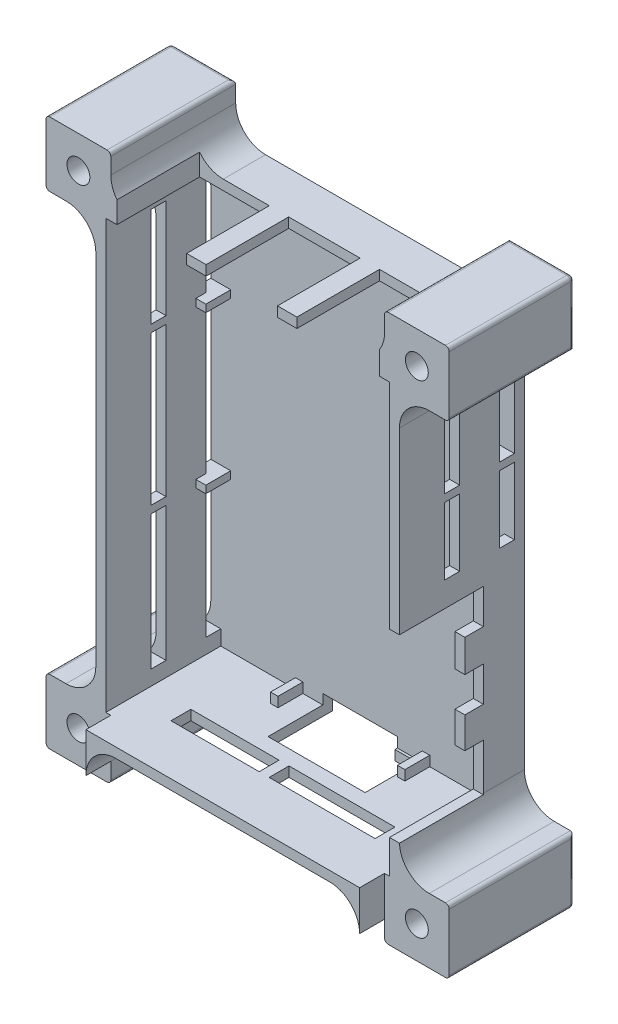
SolidWorks part; units mm, degrees
ref_plane "Front Plane" through (0, 0, 0) normal (0, 0, 1) x (1, 0, 0)
ref_plane "Top Plane" through (0, 0, 0) normal (0, 1, 0) x (1, 0, 0)
ref_plane "Right Plane" through (0, 0, 0) normal (1, 0, 0) x (0, 0, -1)
sketch "Sketch1" plane through (0, 0, 0) normal (0, 0, 1) x (1, 0, 0)
  line L1 (0, 0) -> (61, 0)
  line L2 (0, 0) -> (0, 90)
  line L3 (0, 90) -> (61, 90)
  line L4 (61, 0) -> (61, 90)
  dimension "D1" = 61
  dimension "D2" = 90
extrude "Boss-Extrude1" add sketch "Sketch1" along normal blind 2
sketch "Sketch2" plane through (0, 0, 2) normal (0, 0, 1) x (1, 0, 0)
  line L7 (0, -16.225) -> (0, 16.225) construction
  line L8 (0, 90) -> (0, 0)
  line L9 (2, 90) -> (2, 2)
  line L10 (2, 2) -> (59, 2)
  line L11 (59, 2) -> (59, 90)
  line L12 (2, 88) -> (2, 2)
  line L13 (2, 2) -> (59, 2)
  line L14 (59, 2) -> (59, 88)
  line L15 (0, 0) -> (61, 0)
  line L18 (61, 90) -> (61, 0)
  line L20 (2, 88) -> (59, 88)
  line L21 (0, 90) -> (61, 90)
  dimension "D1" = 2
extrude "Boss-Extrude2" add sketch "Sketch2" along normal blind 6.6
sketch "Sketch3" plane through (0, 0, 2) normal (0, 0, 1) x (1, 0, 0)
  line L0 (59, 2) -> (2, 2) construction
  line L1 (44, 2) -> (42.5, 2)
  line L2 (44, 2) -> (44, 4)
  line L3 (44, 4) -> (42.5, 4)
  line L4 (42.5, 2) -> (42.5, 4)
  line L5 (2, 2) -> (2, 88) construction
  line L6 (17, 2) -> (18.5, 2)
  line L7 (17, 2) -> (17, 4)
  line L8 (17, 4) -> (18.5, 4)
  line L9 (18.5, 2) -> (18.5, 4)
  line L10 (2, 32) -> (4, 32)
  line L11 (2, 32) -> (2, 33.5)
  line L12 (2, 33.5) -> (4, 33.5)
  line L13 (4, 32) -> (4, 33.5)
  line L14 (59, 88) -> (59, 2) construction
  line L15 (59, 32) -> (57, 32)
  line L16 (59, 32) -> (59, 33.5)
  line L17 (59, 33.5) -> (57, 33.5)
  line L18 (57, 32) -> (57, 33.5)
  line L19 (2, 2) -> (2, 88) construction
  line L20 (59, 63.5) -> (57, 63.5)
  line L21 (59, 63.5) -> (59, 65)
  line L22 (59, 65) -> (57, 65)
  line L23 (57, 63.5) -> (57, 65)
  line L24 (2, 63.5) -> (4, 63.5)
  line L25 (2, 63.5) -> (2, 65)
  line L26 (2, 65) -> (4, 65)
  line L27 (4, 63.5) -> (4, 65)
  line L28 (59, 2) -> (2, 2) construction
  dimension "D1" = 1.5
  dimension "D2" = 1.5
  dimension "D3" = 1.5
  dimension "D4" = 1.5
  dimension "D5" = 1.5
  dimension "D6" = 1.5
  dimension "D7" = 2
  dimension "D8" = 2
  dimension "D9" = 2
  dimension "D10" = 2
  dimension "D11" = 2
  dimension "D12" = 2
  dimension "D13" = 30
  dimension "D14" = 30
  dimension "D15" = 30
  dimension "D16" = 30
  dimension "D17" = 15
  dimension "D18" = 15
extrude "Boss-Extrude3" add sketch "Sketch3" along normal blind 5
sketch "Sketch4" plane through (0, 0, 8.6) normal (0, 0, 1) x (1, 0, 0)
  line L1 (61, 90) -> (0, 90)
  line L3 (59, 88) -> (2, 88)
  line L5 (61, 90) -> (61, 0)
  line L6 (0, 90) -> (0, 0)
  line L7 (0, 0) -> (61, 0)
  line L8 (2, 2) -> (59, 2)
  line L9 (2, 88) -> (2, 2)
  line L10 (59, 2) -> (59, 88)
  line L11 (59, 2) -> (59, 88) construction
extrude "Boss-Extrude4" add sketch "Sketch4" along normal blind 16.5
sketch "Sketch5" plane through (0, 90, 0) normal (0, 1, 0) x (1, 0, 0)
  line L1 (57, -8.5) -> (40.4, -8.5)
  line L3 (57, -22.25) -> (40.4, -22.25) construction
  line L4 (40.4, -8.5) -> (40.4, -22.25)
  line L5 (61, 0) -> (0, 0) construction
  line L6 (61, -25.1) -> (0, -25.1) construction
  line L7 (36.5, -25.1) -> (22.15, -25.1)
  line L8 (36.5, -25.1) -> (36.5, -8.5)
  line L9 (36.5, -8.5) -> (22.15, -8.5)
  line L10 (22.15, -25.1) -> (22.15, -8.5)
  line L11 (0, -25.1) -> (0, 0) construction
  line L12 (18.25, -25.1) -> (4.25, -25.1)
  line L13 (18.25, -25.1) -> (18.25, -8.5)
  line L14 (18.25, -8.5) -> (4.25, -8.5)
  line L15 (4.25, -25.1) -> (4.25, -8.5)
  line L17 (57, -25.1) -> (40.4, -25.1)
  line L19 (57, -22.25) -> (40.4, -22.25) construction
  line L20 (40.4, -25.1) -> (40.4, -22.25)
  line L21 (57, -8.5) -> (57, -25.1)
  line L22 (61, -25.1) -> (61, 0) construction
  point P21 (61, -12.55)
  dimension "D2" = 16.6
  dimension "D3" = 13.75
  dimension "D4" = 8.5
  dimension "D5" = 4.25
  dimension "D6" = 3.9
  dimension "D7" = 14
  dimension "D8" = 8.5
  dimension "D9" = 8.5
  dimension "D10" = 3.9
  dimension "D11" = 4
  dimension "D12" = 0
extrude "Cut-Extrude1" cut sketch "Sketch5" against normal blind 2
sketch "Sketch7" plane through (61, 0, 0) normal (1, 0, 0) x (0, 0, -1)
  line L0 (-11.95, 18.25) -> (-11.95, 24.5)
  line L8 (-11.95, 18.25) -> (-8.25, 18.25)
  line L9 (-8.25, 8.75) -> (-8.25, 18.25)
  line L10 (-11.95, 24.5) -> (-8.25, 24.5)
  line L12 (-11.95, 38) -> (-8.25, 38)
  line L14 (-11.95, 31.5) -> (-8.25, 31.5)
  line L18 (-25.1, 0) -> (-25.1, 90) construction
  line L19 (-25.1, 8.75) -> (-25.1, 45)
  line L21 (-11.95, 38) -> (-11.95, 31.5)
  line L22 (-8.25, 8.75) -> (-25.1, 8.75)
  line L23 (-25.1, 45) -> (-8.25, 45)
  line L24 (-25.1, 0) -> (0, 0) construction
  line L25 (-8.25, 24.5) -> (-8.25, 31.5)
  line L26 (-8.25, 38) -> (-8.25, 45)
  line L28 (0, 0) -> (0, 90) construction
  line L29 (0, 33.55) -> (0, -33.55) construction
  line L30 (-2, 85) -> (-5, 85)
  line L31 (-2, 85) -> (-2, 50)
  line L32 (-2, 50) -> (-5, 50)
  line L33 (-5, 85) -> (-5, 50)
  line L34 (-25.1, 90) -> (0, 90) construction
  line L35 (-16, 50) -> (-13, 50)
  line L36 (-16, 50) -> (-16, 63.5)
  line L37 (-16, 63.5) -> (-13, 63.5)
  line L38 (-13, 50) -> (-13, 63.5)
  line L39 (-16, 65) -> (-13, 65)
  line L40 (-16, 65) -> (-16, 85)
  line L41 (-16, 85) -> (-13, 85)
  line L42 (-13, 65) -> (-13, 85)
  point P0 (-8.25, 13.5)
  point P16 (-8.25, 41.5)
  point P18 (-10.1, 18.25)
  point P20 (-8.25, 28)
  dimension "D1" = 9.5
  dimension "D2" = 28
  dimension "D3" = 7
  dimension "D4" = 7
  dimension "D5" = 13.5
  dimension "D6" = 41.5
  dimension "D7" = 3.7
  dimension "D8" = 3.7
  dimension "D9" = 8.25
  dimension "D10" = 0
  dimension "D11" = 0
  dimension "D12" = 2
  dimension "D13" = 5
  dimension "D14" = 3
  dimension "D15" = 35
  dimension "D16" = 3
  dimension "D17" = 8
  dimension "D18" = 0
  dimension "D19" = 1.5
  dimension "D20" = 20
  dimension "D21" = 3
  dimension "D22" = 8
extrude "Cut-Extrude2" cut sketch "Sketch7" against normal blind 2
sketch "Sketch8" plane through (0, 0, 0) normal (0, -1, 0) x (-1, 0, 0)
  line L0 (0, -25.1) -> (0, 0) construction
  line L2 (-22.5, -13) -> (-22.5, -2.5)
  line L3 (-22.5, -2.5) -> (-42, -2.5)
  line L4 (-42, -13) -> (-42, -2.5)
  line L5 (0, 13.805) -> (0, -13.805) construction
  line L6 (-61, -25.1) -> (-61, 0) construction
  line L7 (-33.55, 0) -> (33.55, 0) construction
  line L8 (-22.5, -13) -> (-42, -13)
  line L9 (-10, -20) -> (-27.72, -20)
  line L10 (-10, -20) -> (-10, -16)
  line L11 (-10, -16) -> (-27.72, -16)
  line L12 (-51, -20) -> (-51, -16)
  line L13 (-27.72, -20) -> (-27.72, -16)
  line L14 (-29.72, -20) -> (-29.72, -16)
  line L15 (-29.72, -20) -> (-51, -20)
  line L16 (-29.72, -16) -> (-51, -16)
  dimension "D1" = 22.5
  dimension "D2" = 19
  dimension "D3" = 2.5
  dimension "D4" = 10.5
  dimension "D5" = 3
  dimension "D6" = 4
  dimension "D7" = 10
  dimension "D8" = 10
  dimension "D9" = 2
extrude "Cut-Extrude3" cut sketch "Sketch8" against normal blind 2
sketch "Sketch9" plane through (0, 0, 0) normal (-1, 0, 0) x (0, 0, 1)
  line L0 (0, -33.55) -> (0, 33.55) construction
  line L1 (5, 85) -> (2, 85)
  line L2 (5, 85) -> (5, 5)
  line L3 (5, 5) -> (2, 5)
  line L4 (2, 85) -> (2, 5)
  line L5 (25.1, 90) -> (0, 90) construction
  line L6 (13.805, 0) -> (-13.805, 0) construction
  line L8 (13, 85) -> (16, 85)
  line L9 (13, 85) -> (13, 65)
  line L10 (13, 65) -> (16, 65)
  line L11 (16, 85) -> (16, 65)
  line L12 (16, 63.5) -> (13, 63.5)
  line L13 (16, 63.5) -> (16, 33.5)
  line L14 (16, 33.5) -> (13, 33.5)
  line L15 (13, 63.5) -> (13, 33.5)
  line L16 (13, 32) -> (16, 32)
  line L17 (13, 32) -> (13, 5)
  line L18 (13, 5) -> (16, 5)
  line L19 (16, 32) -> (16, 5)
  dimension "D1" = 2
  dimension "D2" = 3
  dimension "D3" = 5
  dimension "D4" = 5
  dimension "D5" = 1.5
  dimension "D6" = 1.5
  dimension "D7" = 0
  dimension "D8" = 0
  dimension "D9" = 8
  dimension "D10" = 3
  dimension "D11" = 8
  dimension "D12" = 8
  dimension "D13" = 3
  dimension "D14" = 3
  dimension "D15" = 20
  dimension "D16" = 30
extrude "Cut-Extrude4" cut sketch "Sketch9" against normal blind 2
sketch "Sketch10" plane through (0, 0, 25.1) normal (0, 0, 1) x (1, 0, 0)
  line L0 (61, 0) -> (61, 8.75) construction
  line L1 (0, 0) -> (61, 0)
  line L2 (0, 0) -> (0, 2)
  line L3 (0, 2) -> (61, 2)
  line L4 (61, 0) -> (61, 2)
  dimension "D1" = 2
extrude "Boss-Extrude5" add sketch "Sketch10" along normal blind 5
sketch "Sketch12" plane through (2, 0, 0) normal (-1, 0, 0) x (0, 0, 1)
  line L0 (5, 63.5) -> (2, 63.5) construction
  line L1 (2, 65) -> (5, 65)
  line L2 (2, 65) -> (2, 63.5)
  line L3 (2, 63.5) -> (5, 63.5)
  line L4 (5, 65) -> (5, 63.5)
  line L5 (5, 32) -> (2, 32) construction
  line L6 (2, 33.5) -> (5, 33.5)
  line L7 (2, 33.5) -> (2, 32)
  line L8 (2, 32) -> (5, 32)
  line L9 (5, 33.5) -> (5, 32)
extrude "Boss-Extrude6" add sketch "Sketch12" along normal blind 2
sketch "Sketch13" plane through (59, 0, 0) normal (1, 0, 0) x (0, 0, -1)
  line L1 (-2, 63.5) -> (-5, 63.5)
  line L2 (-2, 63.5) -> (-2, 65)
  line L3 (-2, 65) -> (-5, 65)
  line L4 (-5, 63.5) -> (-5, 65)
extrude "Boss-Extrude7" add sketch "Sketch13" along normal blind 2
sketch "Sketch20" plane through (0, 0, 0) normal (0, 0, -1) x (-1, 0, 0)
  line L0 (-61, 90) -> (0, 90) construction
  line L1 (-3, 3) -> (10, 3)
  line L2 (-3, 3) -> (-3, -10)
  line L3 (-3, -10) -> (10, -10)
  line L4 (10, 3) -> (10, -10)
  line L5 (-3, 3) -> (10, -10) construction
  line L6 (-3, -10) -> (10, 3) construction
  line L7 (-58, 87) -> (-71, 87)
  line L8 (-58, 87) -> (-58, 100)
  line L9 (-58, 100) -> (-71, 100)
  line L10 (-71, 87) -> (-71, 100)
  line L11 (-58, 87) -> (-71, 100) construction
  line L12 (-58, 100) -> (-71, 87) construction
  line L13 (-61, 0) -> (-61, 90) construction
  line L14 (0, 0) -> (-61, 0) construction
  line L15 (0, 90) -> (0, 0) construction
  point P4 (3.5, -3.5)
  point P9 (-64.5, 93.5)
  dimension "D1" = 3
  dimension "D2" = 3
  dimension "D3" = 13
  dimension "D4" = 13
  dimension "D5" = 3
  dimension "D6" = 13
  dimension "D7" = 3
  dimension "D8" = 13
extrude "Boss-Extrude8" add sketch "Sketch20" against normal up to surface (25.1 mm away) up to face at (2.0833, 60, 25.1)
sketch "Sketch25" plane through (0, 0, 25.1) normal (0, 0, 1) x (1, 0, 0)
  line L1 (3, 3) -> (-10, 3)
  line L2 (3, 3) -> (3, -10)
  line L3 (3, -10) -> (-10, -10)
  line L4 (-10, 3) -> (-10, -10)
  line L5 (3, 3) -> (-10, -10) construction
  line L6 (3, -10) -> (-10, 3) construction
  line L7 (3, -10) -> (3.25, -10)
  line L8 (3, -10) -> (3, 3)
  line L9 (3, 3) -> (3.25, 3)
  line L10 (3.25, -10) -> (3.25, 3)
  line L11 (3, -10) -> (3.25, 3) construction
  line L12 (3, 3) -> (3.25, -10) construction
  point P4 (-3.5, -3.5)
  point P10 (3.125, -3.5)
  dimension "D1" = 0.25
extrude "Cut-Extrude11" cut sketch "Sketch25" along normal through all contours L2 L1 L4 L3 | L8 L7 L10 L9
sketch "Sketch26" plane through (0, 0, 25.1) normal (0, 0, 1) x (1, 0, 0)
  line L1 (3, 3) -> (2, 3)
  line L2 (3, 3) -> (3, 2)
  line L3 (3, 2) -> (2, 2)
  line L4 (2, 3) -> (2, 2)
  line L5 (3, 3) -> (2, 2) construction
  line L6 (3, 2) -> (2, 3) construction
  line L7 (58, 87) -> (59, 87)
  line L8 (58, 87) -> (58, 88)
  line L9 (58, 88) -> (59, 88)
  line L10 (59, 87) -> (59, 88)
  line L11 (58, 87) -> (59, 88) construction
  line L12 (58, 88) -> (59, 87) construction
  point P4 (2.5, 2.5)
  point P10 (58.5, 87.5)
  dimension "D1" = 1
  dimension "D2" = 1
  dimension "D3" = 1
  dimension "D4" = 1
extrude "Cut-Extrude12" cut sketch "Sketch26" against normal up to surface (23.1 mm away) up to face at (30.4, 40.25, 2)
sketch "Sketch27" plane through (0, 0, 25.1) normal (0, 0, 1) x (1, 0, 0)
  line L0 (64.5, 100) -> (64.5, 87) construction
  line L1 (58, 100) -> (71, 100) construction
  line L2 (71, 87) -> (61, 87) construction
  line L3 (71, 93.5) -> (58, 93.5) construction
  line L4 (71, 100) -> (71, 87) construction
  line L5 (58, 90) -> (58, 100) construction
  line L6 (-3.5, -10) -> (-3.5, 3) construction
  line L7 (3, -10) -> (-10, -10) construction
  line L8 (-10, 3) -> (0, 3) construction
  line L9 (-10, -3.5) -> (3, -3.5) construction
  line L10 (-10, -10) -> (-10, 3) construction
  line L11 (3, 0) -> (3, -10) construction
  circle A0 centre (-3.5, -3.5) radius 2.3
  circle A1 centre (64.5, 93.5) radius 2.3
  dimension "D1" = 4.6
  dimension "D2" = 4.6
extrude "Cut-Extrude13" cut sketch "Sketch27" against normal through all
sketch "Sketch31" plane through (0, 0, 0) normal (0, 0, -1) x (-1, 0, 0)
  line L0 (-71, 100) -> (-71, 87) construction
  line L1 (-61.8731, 88.95) -> (-59.2461, 93.5)
  line L2 (-59.2461, 93.5) -> (-61.8731, 98.05)
  line L3 (-61.8731, 98.05) -> (-67.1269, 98.05)
  line L4 (-67.1269, 98.05) -> (-69.7539, 93.5)
  line L5 (-69.7539, 93.5) -> (-67.1269, 88.95)
  line L6 (-67.1269, 88.95) -> (-61.8731, 88.95)
  line L7 (6.1269, -8.05) -> (8.7539, -3.5)
  line L8 (8.7539, -3.5) -> (6.1269, 1.05)
  line L9 (6.1269, 1.05) -> (0.8731, 1.05)
  line L10 (0.8731, 1.05) -> (-1.7539, -3.5)
  line L11 (-1.7539, -3.5) -> (0.8731, -8.05)
  line L12 (0.8731, -8.05) -> (6.1269, -8.05)
  line L13 (10, -10) -> (10, 3) construction
  circle A0 centre (-64.5, 93.5) radius 4.55 construction
  circle A1 centre (3.5, -3.5) radius 4.55 construction
  dimension "D1" = 9.1
  dimension "D2" = 9.1
  dimension "D3" = 30
  dimension "D4" = 30
extrude "Cut-Extrude17" cut sketch "Sketch31" against normal blind 6
fillet "Fillet3" radius 6 1 edges at (58, 90, 12.55) type face fillet first side face at (29.5687, 90, 15.7375) second side face at (58, 95, 12.55)
fillet "Fillet4" radius 6 1 edges at (61, 87, 12.55) type face fillet first side face at (61, 75, 3.5) second side face at (66, 87, 12.55)
sketch "Sketch33" plane through (0, 0, 25.1) normal (0, 0, 1) x (1, 0, 0)
  line L0 (2, 2) -> (3.25, 2) construction
  line L1 (3.25, 0) -> (3, 0)
  line L2 (3.25, 0) -> (3.25, 2)
  line L3 (3.25, 2) -> (3, 2)
  line L4 (3, 0) -> (3, 2)
  line L5 (3.25, 0) -> (3, 2) construction
  line L6 (3.25, 2) -> (3, 0) construction
  point P4 (3.125, 1)
  dimension "D1" = 0.25
extrude "Boss-Extrude10" add sketch "Sketch33" along normal up to surface (5 mm away) up to face at (32.125, 1, 30.1)
fillet "Fillet7" radius 6 1 edges at (3, 0, 12.55) type face fillet first side face at (3, -5, 12.55) second side face at (18.86, 0, 18)
fillet "Fillet8" radius 6 1 edges at (0, 3, 12.55) type face fillet first side face at (-5, 3, 12.55) second side face at (0, 48.5, 3.5)
sketch "Sketch34" plane through (0, 0, 25.1) normal (0, 0, 1) x (1, 0, 0)
  line L0 (18.25, 90) -> (4.25, 90) construction
  line L1 (59, 3) -> (71, 3)
  line L2 (58, 2) -> (58, -10)
  line L3 (58, -10) -> (71, -10)
  line L4 (71, 3) -> (71, -10)
  line L5 (59, 2) -> (71, -10) construction
  line L6 (58, -10) -> (71, 3) construction
  line L7 (2, 87) -> (-10, 87)
  line L8 (3, 88) -> (3, 100)
  line L9 (3, 100) -> (-10, 100)
  line L10 (-10, 87) -> (-10, 100)
  line L11 (2, 88) -> (-10, 100) construction
  line L12 (3, 100) -> (-10, 87) construction
  line L13 (0, 90) -> (0, 9) construction
  line L14 (61, 0) -> (61, 2) construction
  line L15 (9, 0) -> (61, 0) construction
  line L16 (59, 88) -> (2, 88) construction
  line L17 (2, 88) -> (2, 2) construction
  line L18 (3, 88) -> (2, 88)
  line L19 (2, 88) -> (2, 87)
  line L20 (59, 2) -> (59, 8.75) construction
  line L21 (44, 2) -> (59, 2) construction
  line L22 (59, 2) -> (59, 3)
  line L23 (58, 2) -> (59, 2)
  point P4 (64.5, -3.5)
  point P9 (-3.5, 93.5)
  dimension "D1" = 3
  dimension "D2" = 3
  dimension "D3" = 3
  dimension "D4" = 3
  dimension "D5" = 13
  dimension "D6" = 13
  dimension "D7" = 13
  dimension "D8" = 13
extrude "Boss-Extrude11" add sketch "Sketch34" against normal up to surface (25.1 mm away) up to face at (30.5, 45, 0)
sketch "Sketch35" plane through (0, 0, 25.1) normal (0, 0, 1) x (1, 0, 0)
  line L0 (-3.5, 100) -> (-3.5, 87) construction
  line L1 (3, 100) -> (-10, 100) construction
  line L2 (-10, 87) -> (0, 87) construction
  line L3 (-10, 93.5) -> (3, 93.5) construction
  line L4 (-10, 100) -> (-10, 87) construction
  line L5 (3, 90) -> (3, 100) construction
  line L6 (64.5, -10) -> (64.5, 3) construction
  line L7 (58, -10) -> (71, -10) construction
  line L8 (71, 3) -> (61, 3) construction
  line L9 (71, -3.5) -> (58, -3.5) construction
  line L10 (71, -10) -> (71, 3) construction
  line L11 (58, 0) -> (58, -10) construction
  circle A0 centre (-3.5, 93.5) radius 2.3
  circle A1 centre (64.5, -3.5) radius 2.3
  dimension "D1" = 4.6
  dimension "D2" = 4.6
extrude "Cut-Extrude18" cut sketch "Sketch35" against normal through all
fillet "Fillet9" radius 6 1 edges at (0, 87, 12.55) type face fillet first side face at (-5, 87, 12.55) second side face at (0, 48.5, 3.5)
fillet "Fillet10" radius 6 1 edges at (3, 90, 12.55) type face fillet first side face at (3, 95, 12.55) second side face at (25.2214, 90, 14.4)
fillet "Fillet11" radius 6 1 edges at (61, 3, 12.55) type face fillet first side face at (66, 3, 12.55) second side face at (61, 45.1667, 11.2375)
fillet "Fillet13" radius 0.75 20 edges at (71, -3.5, 0) (64.5, -10, 0) (-3.5, -10, 0) (-10, -3.5, 0) (-10, 93.5, 0) (-3.5, 100, 0) (71, 93.5, 0) (64.5, 100, 0) (71, 87, 12.55) (71, 100, 12.55) (58, 100, 12.55) (3, 100, 12.55) (-10, 100, 12.55) (-10, 87, 12.55) (-10, 3, 12.55) (-10, -10, 12.55) (3, -10, 12.55) (71, 3, 12.55) (58, -10, 12.55) (71, -10, 12.55)
sketch "Sketch36" plane through (0, 0, 0) normal (0, 0, -1) x (-1, 0, 0)
  line L0 (10, 99.25) -> (10, 87.75) construction
  line L1 (-59.2461, -3.5) -> (-61.8731, 1.05)
  line L2 (-61.8731, 1.05) -> (-67.1269, 1.05)
  line L3 (-67.1269, 1.05) -> (-69.7539, -3.5)
  line L4 (-69.7539, -3.5) -> (-67.1269, -8.05)
  line L5 (-67.1269, -8.05) -> (-61.8731, -8.05)
  line L6 (-61.8731, -8.05) -> (-59.2461, -3.5)
  line L7 (-1.7539, 93.5) -> (0.8731, 88.95)
  line L8 (0.8731, 88.95) -> (6.1269, 88.95)
  line L9 (6.1269, 88.95) -> (8.7539, 93.5)
  line L10 (8.7539, 93.5) -> (6.1269, 98.05)
  line L11 (6.1269, 98.05) -> (0.8731, 98.05)
  line L12 (0.8731, 98.05) -> (-1.7539, 93.5)
  line L15 (-70.25, 3) -> (-70.25, -9.25) construction
  circle A0 centre (-64.5, -3.5) radius 4.55 construction
  circle A1 centre (3.5, 93.5) radius 4.55 construction
  dimension "D1" = 30
  dimension "D2" = 30
  dimension "D3" = 9.1
  dimension "D4" = 9.1
extrude "Cut-Extrude19" cut sketch "Sketch36" against normal blind 6
sketch "Sketch38" plane through (0, 0, 25.1) normal (0, 0, 1) x (1, 0, 0)
  line L0 (61, 2) -> (3, 2) construction
  line L1 (69, -8) -> (58, -8)
  line L2 (69, -8) -> (69, 3)
  line L3 (69, 3) -> (58, 3)
  line L4 (58, -8) -> (58, 3)
  line L6 (61, 0) -> (61, 2) construction
  dimension "D1" = 11
  dimension "D2" = 8
  dimension "D3" = 1
extrude "Cut-Extrude20" cut sketch "Sketch38" along normal blind 10
fillet "Fillet14" radius 6 1 edges at (58, 0, 12.55) type face fillet first side face at (40.36, 0, 18) second side face at (58, -4.625, 12.55)
sketch "Sketch39" plane through (0, 0, 0) normal (0, -1, 0) x (1, 0, 0)
  line L0 (9, 0) -> (52, 0) construction
  line L1 (22.5, 2.5) -> (37.5, 2.5)
  line L2 (22.5, 2.5) -> (22.5, 0)
  line L3 (22.5, 0) -> (37.5, 0)
  line L4 (37.5, 2.5) -> (37.5, 0)
  dimension "D1" = 15
extrude "Cut-Extrude21" cut sketch "Sketch39" against normal blind 4
